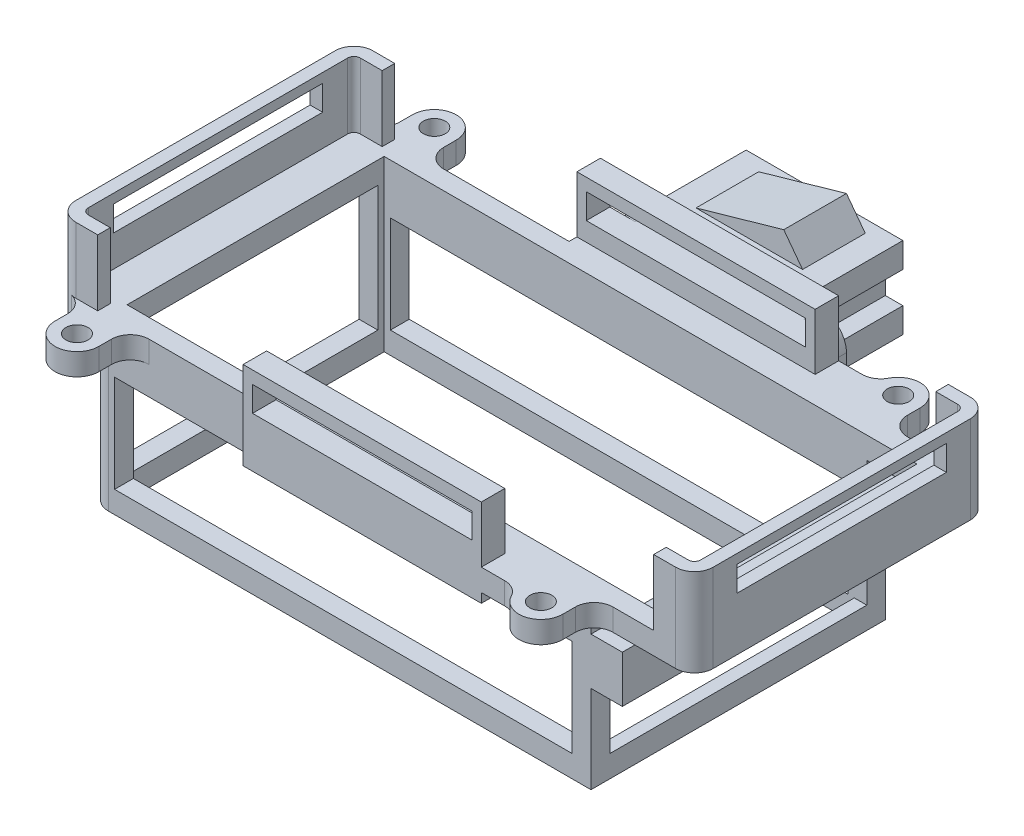
SolidWorks part; units mm, degrees
material "AISI 1045 钢，冷拔"
ref_plane "前视基准面" through (0, 0, 0) normal (0, 0, 1) x (1, 0, 0)
ref_plane "上视基准面" through (0, 0, 0) normal (0, 1, 0) x (1, 0, 0)
ref_plane "右视基准面" through (0, 0, 0) normal (1, 0, 0) x (0, 0, -1)
sketch "草图1" plane through (0, 0, 0) normal (0, 1, 0) x (1, 0, 0)
  line L1 (-40, 23.5) -> (40, 23.5)
  line L2 (-40, 23.5) -> (-40, -23.5)
  line L3 (-40, -23.5) -> (40, -23.5)
  line L4 (40, 23.5) -> (40, -23.5)
  line L5 (-40, 23.5) -> (40, -23.5) construction
  line L6 (-40, -23.5) -> (40, 23.5) construction
  point P0 (0, 0)
  dimension "D1" = 47
  dimension "D2" = 80
extrude "凸台-拉伸1" add sketch "草图1" along normal blind 23.5
sketch "草图2" plane through (0, 23.5, 0) normal (0, 1, 0) x (1, 0, 0)
  line L0 (0, 0) -> (17.7347, 0) construction
  line L1 (-37, 28.5) -> (37, 28.5)
  line L2 (-37, 28.5) -> (-37, -28.5)
  line L3 (-37, -28.5) -> (37, -28.5)
  line L4 (37, 28.5) -> (37, -28.5)
  line L5 (-37, 28.5) -> (37, -28.5) construction
  line L6 (-37, -28.5) -> (37, 28.5) construction
  line L7 (0, 0) -> (0, 11.3891) construction
  line L8 (-40, -23.5) -> (40, -23.5) construction
  line L9 (-45, 23.5) -> (56.5, 23.5)
  line L10 (-45, 23.5) -> (-45, -23.5)
  line L11 (-45, -23.5) -> (56.5, -23.5)
  line L12 (56.5, 23.5) -> (56.5, -23.5)
  line L13 (40, 23.5) -> (-40, 23.5) construction
  line L14 (-40, 23.5) -> (-40, -23.5) construction
  line L15 (-40.5, 28.5) -> (-40.5, 23.5)
  line L16 (-33.5, 28.5) -> (-33.5, 23.5)
  line L17 (33.5, 28.5) -> (33.5, 23.5)
  line L18 (40.5, 28.5) -> (40.5, 23.5)
  line L19 (-10.5, 23.5) -> (-10.5, 28.5)
  line L20 (40.5, -28.5) -> (40.5, -23.5)
  line L21 (33.5, -28.5) -> (33.5, -23.5)
  line L22 (-33.5, -28.5) -> (-33.5, -23.5)
  line L23 (-40.5, -28.5) -> (-40.5, -23.5)
  line L24 (-10.5, -23.5) -> (-10.5, -28.5)
  circle A0 centre (-37, 28.5) radius 3.5
  circle A1 centre (37, 28.5) radius 3.5
  circle A2 centre (37, -28.5) radius 3.5
  circle A3 centre (-37, -28.5) radius 3.5
  point P0 (0, 0)
  line M2 (40, 23.5) -> (-40, 23.5)
  line M4 (-40, -23.5) -> (40, -23.5)
  dimension "D3" = 7
  dimension "D1" = 74
  dimension "D2" = 57
  dimension "D4" = 0
  dimension "D5" = 0
  dimension "D6" = 5
  dimension "D7" = 101.5
  dimension "D8" = 51
extrude "凸台-拉伸2" add sketch "草图2" along normal blind 3.5 contours L19 L9 L17 L1 | L24 L3 L21 M4 | A2 L4 L11 L21 | A2 L20 L11 L4 M4 | L4 A1 L17 M2 | L18 A1 L4 L9 M2 | L2 A3 L22 M4 | L23 A3 L2 L11 M4 | A0 L15 L9 L2 M2 | A0 L2 L9 L16 | L10 L11 L12 L9 | A1 | A0 | A3 | A2 region at (-34.9269, 23.5, -24.7611) region at (-39.0731, 23.5, -24.7611) region at (11.5, 23.5, -26) region at (34.9269, 23.5, -24.7611) region at (-34.9269, 23.5, 24.7611) region at (-39.0731, 23.5, 24.7611) region at (39.0731, 23.5, -24.7611) region at (11.5, 23.5, 26) region at (39.0731, 23.5, 24.7611) region at (34.9269, 23.5, 24.7611)
sketch "草图19" plane through (0, 27, 0) normal (0, 1, 0) x (1, 0, 0)
  line L0 (0, 0) -> (13.6064, 0) construction
  line L1 (0, 0) -> (0, 13.0678) construction
  circle A0 centre (-37, 28.5) radius 1.75
  circle A1 centre (37, 28.5) radius 1.75
  circle A2 centre (37, -28.5) radius 1.75
  circle A3 centre (-37, -28.5) radius 1.75
  dimension "D1" = 3.5
extrude "切除-拉伸7" cut sketch "草图19" against normal through all
fillet "圆角2" radius 3 2 edges at (-40, 11.75, -23.5) (-40, 11.75, 23.5)
sketch "草图3" plane through (0, 27, 0) normal (0, 1, 0) x (1, 0, 0)
  line L0 (-45, 23.5) -> (-45, -23.5) construction
  line L1 (-37, 20.5) -> (48, 20.5)
  line L2 (-37, 20.5) -> (-37, -20.5)
  line L3 (-37, -20.5) -> (48, -20.5)
  line L4 (48, 20.5) -> (48, -20.5)
  line L5 (56.5, 23.5) -> (56.5, -23.5) construction
  line L6 (-33.5, 23.5) -> (-10.5, 23.5) construction
  line L7 (-33.5, -23.5) -> (-10.5, -23.5) construction
  dimension "D1" = 8
  dimension "D2" = 8.5
  dimension "D3" = 3
  dimension "D4" = 3
extrude "切除-拉伸1" cut sketch "草图3" against normal blind 23.5
sketch "草图4" plane through (0, 0, 0) normal (0, -1, 0) x (1, 0, 0)
  line L0 (40, 23.5) -> (40, -23.5) construction
  line L1 (-37, 20.5) -> (38, 20.5)
  line L2 (-37, 20.5) -> (-37, -20.5)
  line L3 (-37, -20.5) -> (38, -20.5)
  line L4 (38, 20.5) -> (38, -20.5)
  line L5 (-10.5, 23.5) -> (40, 23.5) construction
  line L6 (40, -23.5) -> (-37, -23.5) construction
  line L7 (-40, -20.5) -> (-40, 20.5) construction
  dimension "D1" = 2
  dimension "D2" = 3
  dimension "D3" = 3
  dimension "D4" = 3
extrude "切除-拉伸2" cut sketch "草图4" against normal blind 4
sketch "草图5" plane through (0, 0, 23.5) normal (0, 0, 1) x (1, 0, 0)
  line L0 (-40, 0) -> (-40, 23.5) construction
  line L1 (-36, 19) -> (37, 19)
  line L2 (-36, 19) -> (-36, 3.5)
  line L3 (-36, 3.5) -> (37, 3.5)
  line L4 (37, 19) -> (37, 3.5)
  line L5 (40, 23.5) -> (40, 0) construction
  line L6 (-37, 0) -> (40, 0) construction
  line L7 (-33.5, 27) -> (-10.5, 27) construction
  dimension "D1" = 4
  dimension "D2" = 3
  dimension "D3" = 3.5
  dimension "D4" = 8
extrude "切除-拉伸3" cut sketch "草图5" against normal through all
sketch "草图6" plane through (-40, 0, 0) normal (-1, 0, 0) x (0, 0, 1)
  line L0 (-23.5, 0) -> (-23.5, 23.5) construction
  line L1 (-19.5, 23.5) -> (19.5, 23.5)
  line L2 (-19.5, 23.5) -> (-19.5, 3.5)
  line L3 (-19.5, 3.5) -> (19.5, 3.5)
  line L4 (19.5, 23.5) -> (19.5, 3.5)
  line L5 (23.5, 23.5) -> (23.5, 0) construction
  line L6 (-23.5, 23.5) -> (23.5, 23.5) construction
  line L7 (-20.5, 0) -> (20.5, 0) construction
  dimension "D1" = 4
  dimension "D2" = 4
  dimension "D3" = 0
  dimension "D4" = 3.5
extrude "切除-拉伸4" cut sketch "草图6" against normal blind 4
sketch "草图9" plane through (0, 0, 28.5) normal (0, 0, 1) x (1, 0, 0)
  line L1 (-10.5, 22) -> (27.5, 22)
  line L2 (-10.5, 22) -> (-10.5, 27)
  line L3 (-10.5, 27) -> (27.5, 27)
  line L4 (27.5, 22) -> (27.5, 27)
  line L5 (-10.5, 27) -> (33.5, 27) construction
  dimension "D1" = 38
  dimension "D3" = 5
extrude "凸台-拉伸3" add sketch "草图9" against normal up to next
sketch "草图10" plane through (0, 0, 28.5) normal (0, 0, 1) x (1, 0, 0)
  line L0 (-10.5, 22) -> (27.5, 22) construction
  line L1 (-10.5, 27) -> (27.5, 27)
  line L2 (-10.5, 27) -> (-10.5, 36)
  line L3 (-10.5, 36) -> (27.5, 36)
  line L4 (27.5, 27) -> (27.5, 36)
  dimension "D1" = 38
  dimension "D2" = 14
extrude "凸台-拉伸4" add sketch "草图10" against normal blind 3.75
sketch "草图11" plane through (0, 0, 28.5) normal (0, 0, 1) x (1, 0, 0)
  line L0 (27.5, 36) -> (-10.5, 36) construction
  line L1 (-9, 34) -> (26, 34)
  line L2 (-9, 34) -> (-9, 30)
  line L3 (-9, 30) -> (26, 30)
  line L4 (26, 34) -> (26, 30)
  line L5 (-10.5, 36) -> (-10.5, 22) construction
  line L6 (27.5, 27) -> (27.5, 36) construction
  line L7 (-10.5, 22) -> (27.5, 22) construction
  dimension "D1" = 2
  dimension "D2" = 1.5
  dimension "D3" = 1.5
  dimension "D4" = 8
extrude "切除-拉伸5" cut sketch "草图11" against normal blind 3.75
mirror "镜向1" about plane through (0, 0, 0) normal (0, 0, 1) of "切除-拉伸5", "凸台-拉伸4", "凸台-拉伸3"
fillet "圆角3" radius 3 8 edges at (40.5, 25.25, 23.5) (33.5, 25.25, 28.5) (33.5, 25.25, -28.5) (40.5, 25.25, -23.5)
fillet "圆角4" radius 3 4 edges at (56.5, 25.25, 23.5) (56.5, 25.25, -23.5) (-45, 25.25, -23.5) (-45, 25.25, 23.5)
sketch "草图12" plane through (0, 27, 0) normal (0, 1, 0) x (1, 0, 0)
  line L0 (-45, 20.6905) -> (-45, -20.6905)
  line L1 (-42, 23.6905) -> (-38.5, 23.6905)
  line L2 (0, 0) -> (9.3281, 0) construction
  line L3 (53.5, 23.5) -> (50, 23.5)
  line L4 (-42, -23.6905) -> (-38.5, -23.6905)
  line L5 (-42, 21.6905) -> (-38.5, 21.6905)
  line L6 (-43, 20.6905) -> (-43, -20.6905)
  line L7 (-42, -21.6905) -> (-38.5, -21.6905)
  line L8 (-38.5, 23.6905) -> (-38.5, 21.6905)
  line L9 (-38.5, -21.6905) -> (-38.5, -23.6905)
  line L10 (43.5, 23.5) -> (53.5, 23.5) construction
  line L11 (56.5, 20.5) -> (56.5, -20.5)
  line L12 (53.5, -23.5) -> (50, -23.5)
  line L13 (53.5, -21.5) -> (50, -21.5)
  line L14 (54.5, 20.5) -> (54.5, -20.5)
  line L15 (53.5, 21.5) -> (50, 21.5)
  line L16 (50, 23.5) -> (50, 21.5)
  line L17 (50, -21.5) -> (50, -23.5)
  arc A0 (-42, 23.6905) -> (-45, 20.6905) centre (-42, 20.6905) ccw
  arc A1 (-42, -23.6905) -> (-45, -20.6905) centre (-42, -20.6905) cw
  arc A2 (-42, 21.6905) -> (-43, 20.6905) centre (-42, 20.6905) ccw
  arc A3 (-42, -21.6905) -> (-43, -20.6905) centre (-42, -20.6905) cw
  arc A4 (56.5, 20.5) -> (53.5, 23.5) centre (53.5, 20.5) ccw
  arc A5 (56.5, -20.5) -> (53.5, -23.5) centre (53.5, -20.5) cw
  arc A6 (54.5, -20.5) -> (53.5, -21.5) centre (53.5, -20.5) cw
  arc A7 (54.5, 20.5) -> (53.5, 21.5) centre (53.5, 20.5) ccw
  dimension "D2" = 2
  dimension "D1" = 6.5
  dimension "D3" = 6.5
  dimension "D4" = 2
extrude "凸台-拉伸5" add sketch "草图12" along normal blind 10.5
sketch "草图13" plane through (-45, 0, 0) normal (-1, 0, 0) x (0, 0, 1)
  line L0 (-20.6905, 37.5) -> (20.6905, 37.5) construction
  line L1 (-16.6905, 36) -> (16.6905, 36)
  line L2 (-16.6905, 36) -> (-16.6905, 32)
  line L3 (-16.6905, 32) -> (16.6905, 32)
  line L4 (16.6905, 36) -> (16.6905, 32)
  line L5 (23.6905, 37.5) -> (23.6905, 27) construction
  line L6 (-23.6905, 37.5) -> (-23.6905, 27) construction
  line L7 (-20.6905, 23.5) -> (20.6905, 23.5) construction
  dimension "D1" = 1.5
  dimension "D2" = 7
  dimension "D3" = 7
  dimension "D4" = 8.5
extrude "切除-拉伸6" cut sketch "草图13" against normal through all
sketch "草图14" plane through (40, 0, 0) normal (1, 0, 0) x (0, 0, -1)
  line L0 (-23.5, 23.5) -> (-23.5, 0) construction
  line L1 (-23.5, 21.5) -> (23.5, 21.5)
  line L2 (-23.5, 21.5) -> (-23.5, 14)
  line L3 (-23.5, 14) -> (23.5, 14)
  line L4 (23.5, 21.5) -> (23.5, 14)
  line L5 (23.5, 23.5) -> (23.5, 0) construction
  line L6 (-23.5, 0) -> (23.5, 0) construction
  dimension "D1" = 7.5
  dimension "D2" = 21.5
extrude "凸台-拉伸6" add sketch "草图14" along normal blind 5
sketch "草图15" plane through (0, 0, -28.5) normal (0, 0, 1) x (1, 0, 0)
  line L0 (-9, 30) -> (26, 30) construction
  line L1 (-9, 30) -> (26, 30)
  line L2 (-9, 30) -> (-9, 19)
  line L3 (-9, 19) -> (26, 19)
  line L4 (26, 30) -> (26, 19)
  line L5 (-9, 30) -> (26, 19) construction
  line L6 (-9, 19) -> (26, 30) construction
  line L7 (-10.5, 22) -> (27.5, 22) construction
  point P0 (8.5, 24.5)
  point P7 (8.5, 22)
  dimension "D1" = 35
  dimension "D2" = 11
  dimension "D3" = 0
  dimension "D4" = 0
extrude "凸台-拉伸7" add sketch "草图15" against normal blind 2.75
sketch "草图16" plane through (0, 0, -31.25) normal (0, 0, -1) x (-1, 0, 0)
  line L0 (9, 19) -> (-26, 19) construction
  line L1 (-21, 32) -> (4, 32)
  line L2 (-21, 32) -> (-21, 19)
  line L3 (-21, 19) -> (4, 19)
  line L4 (4, 32) -> (4, 19)
  line L5 (-21, 32) -> (4, 19) construction
  line L6 (-21, 19) -> (4, 32) construction
  point P0 (-8.5, 25.5)
  point P7 (-8.5, 19)
  dimension "D1" = 25
  dimension "D2" = 13
  dimension "D3" = 0
  dimension "D4" = 0
extrude "凸台-拉伸8" add sketch "草图16" along normal blind 14
sketch "草图21" plane through (0, 0, -45.25) normal (0, 0, -1) x (-1, 0, 0)
  line L0 (-21, 30) -> (-21, 19) construction
  line L1 (-21, 28) -> (-18.2, 28)
  line L2 (-21, 28) -> (-21, 23)
  line L3 (-21, 23) -> (-18.2, 23)
  line L4 (-18.2, 28) -> (-18.2, 23)
  line L5 (4, 32) -> (-21, 32) construction
  line L6 (-8.5, 32) -> (-8.5, 23.9515) construction
  line L7 (1.2, 28) -> (1.2, 23)
  line L8 (4, 23) -> (1.2, 23)
  line L9 (4, 28) -> (4, 23)
  line L10 (4, 28) -> (1.2, 28)
  dimension "D1" = 4
  dimension "D2" = 5
  dimension "D3" = 2.8
extrude "切除-拉伸8" cut sketch "草图21" against normal blind 14
sketch "草图20" plane through (0, 0, -31.25) normal (0, 0, -1) x (-1, 0, 0)
  line L0 (-8.5, 32) -> (-8.5, 22.6288) construction
  line L2 (-26, 19) -> (-26, 30) construction
  line L3 (4, 32) -> (-21, 32) construction
  circle A0 centre (-22.5, 24.5) radius 2.35
  circle A1 centre (5.5, 24.5) radius 2.35
  point P8 (-26, 24.5)
  dimension "D1" = 4.7
  dimension "D2" = 28
  dimension "D3" = 0
extrude "凸台-拉伸10" add sketch "草图20" along normal blind 1
fillet "圆角5" radius 4 4 edges at (26, 19, -29.875) (26, 30, -29.875) (-9, 19, -29.875) (-9, 30, -29.875)
sketch "草图17" plane through (0, 0, -45.25) normal (0, 0, -1) x (-1, 0, 0)
  line L0 (-17, 32) -> (-14, 36)
  line L1 (4, 32) -> (-21, 32) construction
  line L2 (-14, 36) -> (0, 32)
  line L3 (0, 32) -> (-17, 32)
  line L4 (-21, 32) -> (-21, 28) construction
  line L5 (4, 19) -> (4, 23) construction
  line L6 (-27.5, 36) -> (10.5, 36) construction
  dimension "D1" = 4
  dimension "D2" = 4
  dimension "D3" = 0
  dimension "D4" = 3
extrude "凸台-拉伸9" add sketch "草图17" against normal blind 10 from offset 2 offset against normal yes
